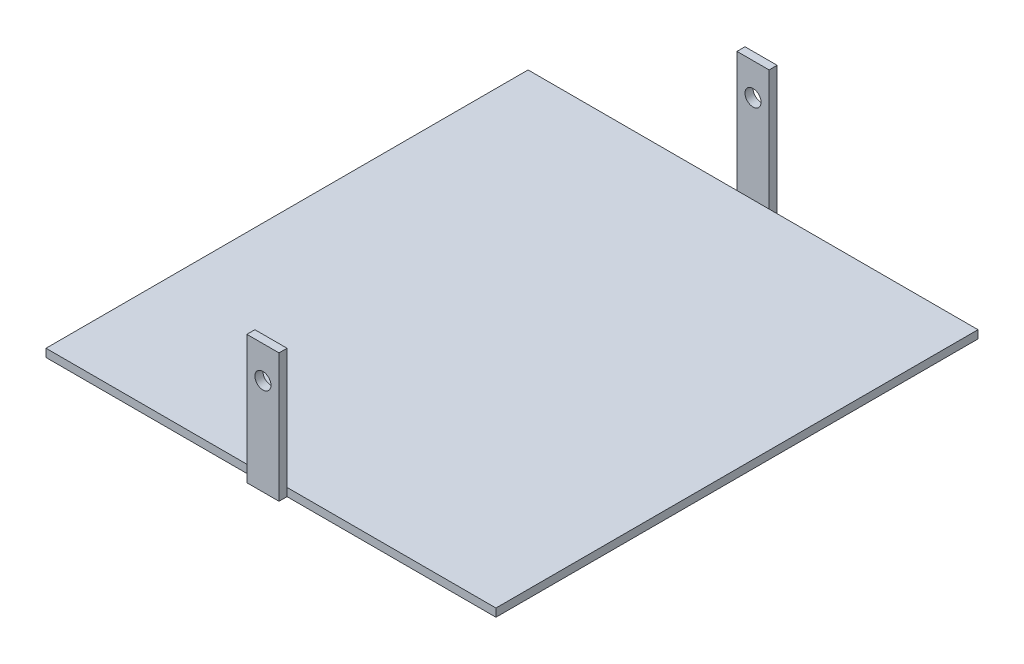
SolidWorks part; units mm, degrees
material "Maple"
ref_plane "Front Plane" through (0, 0, 0) normal (0, 0, 1) x (1, 0, 0)
ref_plane "Top Plane" through (0, 0, 0) normal (0, 1, 0) x (1, 0, 0)
ref_plane "Right Plane" through (0, 0, 0) normal (1, 0, 0) x (0, 0, -1)
sketch "Sketch1" plane through (0, 0, 0) normal (0, 1, 0) x (1, 0, 0)
  line L1 (0, 0) -> (280, 0)
  line L2 (0, 0) -> (0, 300)
  line L3 (0, 300) -> (280, 300)
  line L4 (280, 0) -> (280, 300)
  dimension "D1" = 300
  dimension "D2" = 280
extrude "Boss-Extrude1" add sketch "Sketch1" along normal blind 5
sketch "Sketch2" plane through (0, 0, 0) normal (0, 0, 1) x (1, 0, 0)
  line L0 (0, 0) -> (280, 0) construction
  line L1 (130, 80) -> (150, 80)
  line L2 (130, 80) -> (130, 0)
  line L3 (130, 0) -> (150, 0)
  line L4 (150, 80) -> (150, 0)
  line L5 (280, 5) -> (280, 0) construction
  circle A0 centre (140, 60) radius 5
  dimension "D5" = 60
  dimension "D7" = 10
  dimension "D1" = 80
  dimension "D2" = 20
  dimension "D3" = 130
  dimension "D4" = 130
  dimension "D6" = 10
extrude "Boss-Extrude2" add sketch "Sketch2" along normal blind 5
ref_plane "Plane1" through (0, 0, -150) normal (0, 0, 1) x (1, 0, 0)
mirror "Mirror1" about plane through (0, 0, -150) normal (0, 0, 1) of "Boss-Extrude2"
ref_point "Point1"
ref_point "Point2"
ref_axis "Axis1" through (140, 60, -300) along (0, 0, 1)
